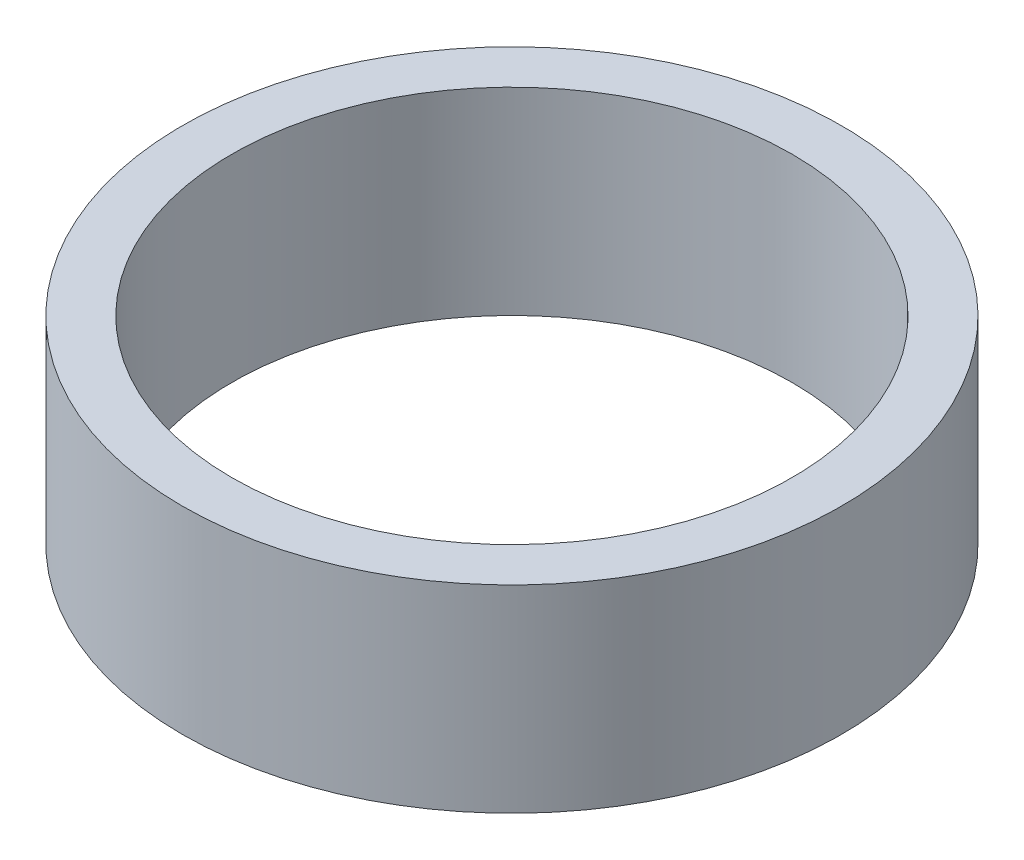
SolidWorks part; units mm, degrees
ref_plane "Front Plane" through (0, 0, 0) normal (0, 0, 1) x (1, 0, 0)
ref_plane "Top Plane" through (0, 0, 0) normal (0, 1, 0) x (1, 0, 0)
ref_plane "Right Plane" through (0, 0, 0) normal (1, 0, 0) x (0, 0, -1)
sketch "Sketch1" plane through (0, 0, 0) normal (0, 1, 0) x (1, 0, 0)
  circle A0 centre (0, 0) radius 50
  dimension "FLANGE_OD" = 100
extrude "Boss-Extrude1" add sketch "Sketch1" along normal blind 30
sketch "Sketch2" plane through (0, 0, 0) normal (0, 1, 0) x (1, 0, 0)
  circle A0 centre (0, 0) radius 42.5
  dimension "BORE_D" = 85
extrude "Cut-Extrude1" cut sketch "Sketch2" along normal through all
sketch "Sketch3" plane through (0, 30, 0) normal (0, 1, 0) x (1, 0, 0)
  circle A0 centre (0, 0) radius 22.5212 construction
  circle A1 centre (-22.5212, 0) radius 1.5
  dimension "BOLT_D" = 3
  dimension "BOLT_PCD" = 45.0423
extrude "Cut-Extrude2" cut sketch "Sketch3" against normal blind 18.5597 rebuild error yes
pattern_circular "CirPattern1" count 8 over 360 rebuild error yes
